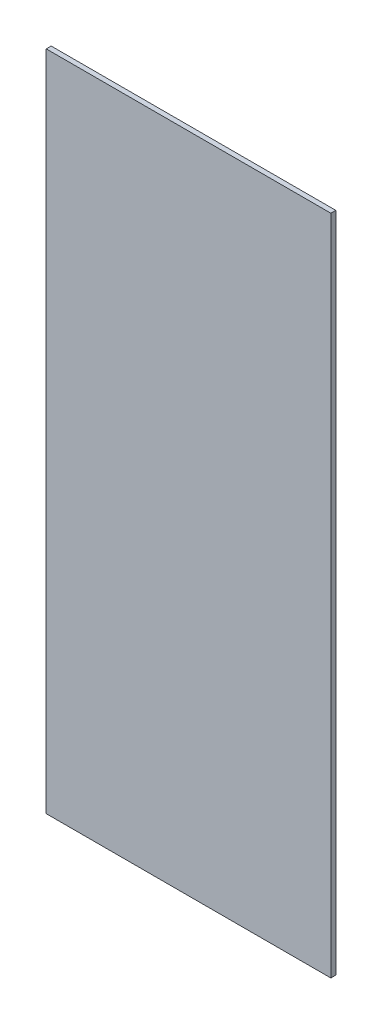
SolidWorks part; units mm, degrees
ref_plane "Front Plane" through (0, 0, 0) normal (0, 0, 1) x (1, 0, 0)
ref_plane "Top Plane" through (0, 0, 0) normal (0, 1, 0) x (1, 0, 0)
ref_plane "Right Plane" through (0, 0, 0) normal (1, 0, 0) x (0, 0, -1)
sketch "Sketch1" plane through (0, 0, 0) normal (0, 0, 1) x (1, 0, 0)
  line L1 (-287.5, 669) -> (287.5, 669)
  line L2 (-287.5, 669) -> (-287.5, -669)
  line L3 (-287.5, -669) -> (287.5, -669)
  line L4 (287.5, 669) -> (287.5, -669)
  line L5 (-287.5, 669) -> (287.5, -669) construction
  line L6 (-287.5, -669) -> (287.5, 669) construction
  point P0 (0, 0)
  dimension "D1" = 575
  dimension "D2" = 1338
extrude "Boss-Extrude1" add sketch "Sketch1" along normal blind 10
